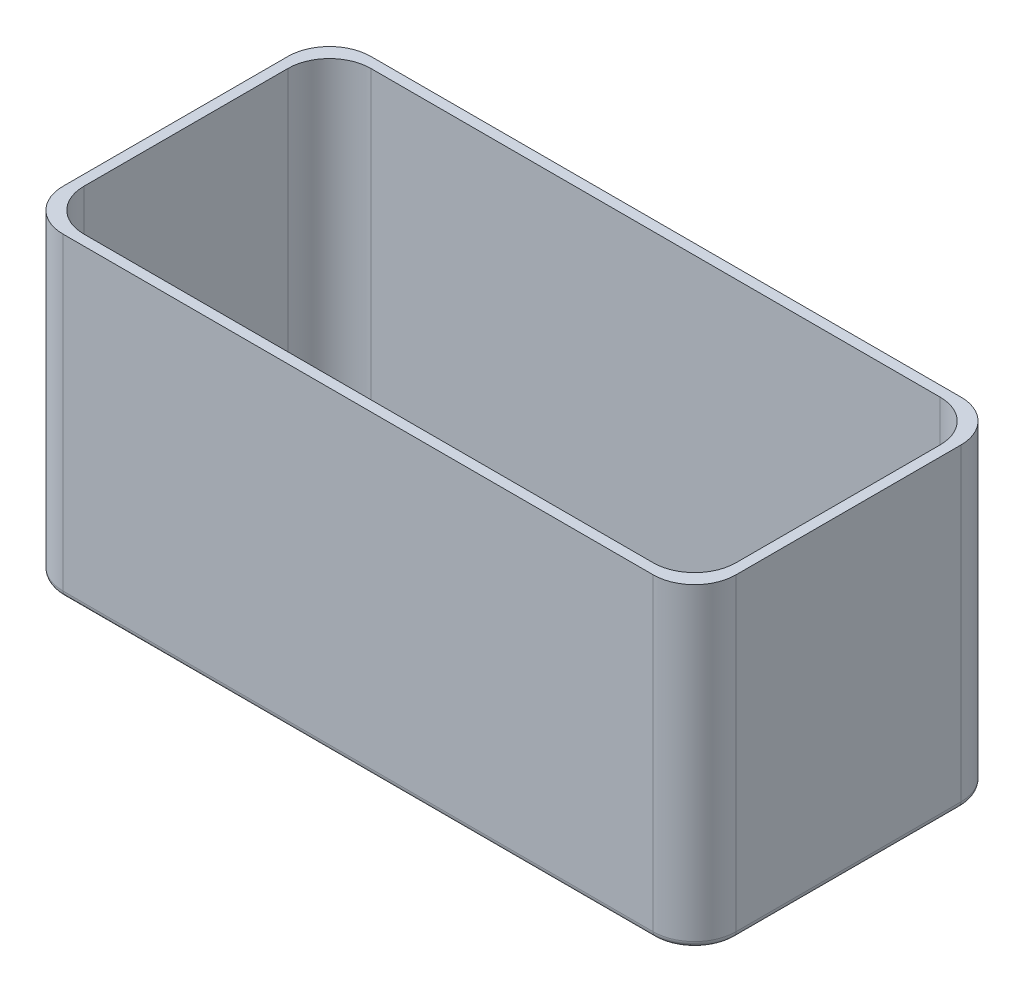
SolidWorks part; units mm, degrees
ref_plane "Front Plane" through (0, 0, 0) normal (0, 0, 1) x (1, 0, 0)
ref_plane "Top Plane" through (0, 0, 0) normal (0, 1, 0) x (1, 0, 0)
ref_plane "Right Plane" through (0, 0, 0) normal (1, 0, 0) x (0, 0, -1)
sketch "Sketch4" plane through (0, 0, 0) normal (0, 1, 0) x (1, 0, 0)
  line L0 (25.8, 11.8) -> (-25.8, 11.8)
  line L1 (25, 11) -> (-25, 11)
  line L2 (25, 11) -> (25, -11)
  line L3 (25, -11) -> (-25, -11)
  line L4 (-25, 11) -> (-25, -11)
  line L5 (25, 11) -> (-25, -11) construction
  line L6 (25, -11) -> (-25, 11) construction
  line L7 (-25.8, 11.8) -> (-25.8, -11.8)
  line L8 (25.8, -11.8) -> (-25.8, -11.8)
  line L9 (25.8, 11.8) -> (25.8, -11.8)
  point P0 (0, 0)
  dimension "D1" = 22
  dimension "D2" = 50
  dimension "D3" = 0.8
extrude "Boss-Extrude2" add sketch "Sketch4" along normal blind 24.2
extrude "Boss-Extrude3" add sketch "Sketch4<2>" along normal blind 0.8 contours L1 L4 L3 L2 region at (0, 0, 0)
sketch "Sketch4<2>" plane through (0, 0, 0) normal (0, 1, 0) x (1, 0, 0) same geometry as "Sketch4"
fillet "Fillet3" radius 3.18 8 edges at (25.8, 12.1, 11.8) (25.8, 12.1, -11.8) (25, 12.5, -11) (-25, 12.5, 11) (-25, 12.5, -11) (25, 12.5, 11) (-25.8, 12.1, 11.8) (-25.8, 12.1, -11.8)
fillet "Fillet4" radius 0.5 16 edges at (-24.8686, 0, 10.8686) (-25.8, 0, 0) (-24.8686, 0, -10.8686) (0, 0, -11.8) (24.8686, 0, -10.8686) (25.8, 0, 0) (24.8686, 0, 10.8686) (-24.0686, 0.8, -10.0686) (0, 0.8, -11) (24.0686, 0.8, -10.0686) (25, 0.8, 0) (24.0686, 0.8, 10.0686) (0, 0.8, 11) (-24.0686, 0.8, 10.0686) (0, 0, 11.8) (-25, 0.8, 0)
